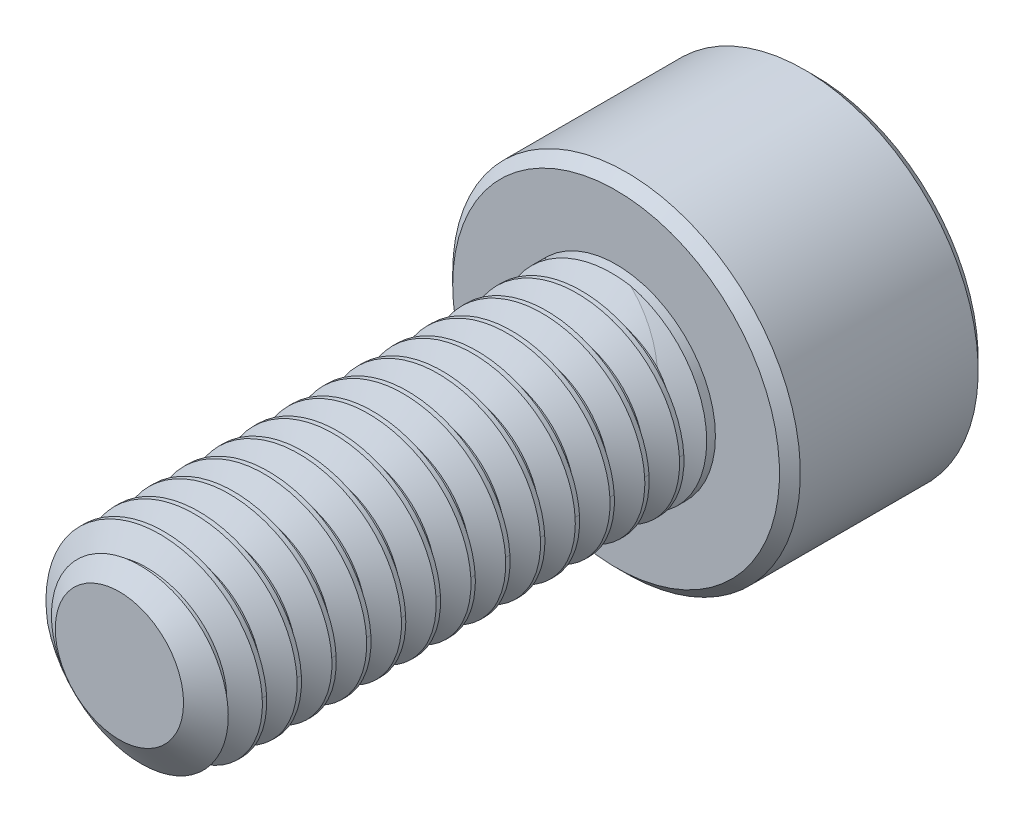
SolidWorks part; units mm, degrees
ref_plane "Front Plane" through (0, 0, 0) normal (0, 0, 1) x (1, 0, 0)
ref_plane "Top Plane" through (0, 0, 0) normal (0, 1, 0) x (1, 0, 0)
ref_plane "Right Plane" through (0, 0, 0) normal (1, 0, 0) x (0, 0, -1)
sketch "Sketch1" plane through (0, 0, 0) normal (0, 0, 1) x (1, 0, 0)
  circle A0 centre (0, 0) radius 2
  dimension "OD" = 4
extrude "Extrude1" add sketch "Sketch1" against normal blind 10
sketch "Sketch2" plane through (0, 0, 0) normal (0, 0, 1) x (1, 0, 0)
  circle A0 centre (0, 0) radius 2 construction
  circle A1 centre (0, 0) radius 2
curve "Helix/Spiral1" pitch 0.7 height 10.7 radius 2 centre (0, 0, 0) axis (0, 0, -1) start towards (0, 1, 0) parameters "pitch"=0.7
sketch "Sketch3" plane through (0, 0, 0) normal (1, 0, 0) x (0, 0, -1)
  line L0 (-0.6125, 2) -> (-0.35, 1.5453)
  line L1 (-0.35, 1.5453) -> (-0.2625, 1.5453)
  line L2 (-0.2625, 1.5453) -> (0, 2)
  line L3 (-0.6125, 2) -> (0, 2)
  line L4 (-0.3063, 2) -> (-0.3063, 1.5453) construction
  line L5 (-0.4813, 1.7727) -> (-0.1313, 1.7727) construction
  line L6 (0, 2) -> (0, -2) construction
  line L7 (0, -2) -> (10, -2) construction
  point P11 (3.15, -2)
  dimension "D1" = 0.0875
  dimension "D2" = 0.35
  dimension "D3" = 60
  dimension "D4" = 3.15
sweep "Cut-Sweep1" cut profiles "Sketch3" path "Helix/Spiral1" align with end faces yes
sketch "Sketch4" plane through (0, 0, 0) normal (1, 0, 0) x (0, 0, -1)
  line L0 (0.4962, 2) -> (0, 1.2913)
  line L1 (0, 1.2913) -> (0, 2)
  line L2 (0.4962, 2) -> (0, 2)
  line L3 (-0.6125, 2) -> (0, 2) construction
  line L4 (0, 0) -> (7.0209, 0) construction
  dimension "D1" = 55
  dimension "D2" = 0.254
revolve "Cut-Revolve1" cut sketch "Sketch4" angle 360 about L4
sketch "Sketch5" plane through (0, 0, 0) normal (1, 0, 0) x (0, 0, -1)
  line L0 (10, 0.3311) -> (10, 1.814) construction
  line L1 (10, 2) -> (0.1203, 2)
  line L2 (10, 2) -> (10, 0)
  line L3 (10, 0) -> (0.0001, 0)
  line L4 (0.0001, 1.6698) -> (0.0001, 0)
  line L5 (0.1203, 2) -> (0.0001, 1.6698)
  line L6 (0, 0) -> (9.9695, 0) construction
  point P3 (0.0001, 2)
  point P10 (0.0001, 2)
  dimension "D1" = 0.3302
  dimension "Thread min" = 0.0001
  dimension "D3" = 20
revolve "partially thread" [suppressed] add sketch "Sketch5" angle 360 about L6
sketch "Sketch6" plane through (0, 0, -10) normal (0, 0, -1) x (-1, 0, 0)
  circle A0 centre (0, 0) radius 3.5
  dimension "head dia" = 7
extrude "Extrude2" add sketch "Sketch6" along normal blind 4
sketch "Sketch7" plane through (0, 0, -14) normal (0, 0, -1) x (-1, 0, 0)
  line L1 (0, 1.7321) -> (-1.5, 0.866)
  line L2 (-1.5, 0.866) -> (-1.5, -0.866)
  line L3 (-1.5, -0.866) -> (0, -1.7321)
  line L4 (0, -1.7321) -> (1.5, -0.866)
  line L5 (1.5, -0.866) -> (1.5, 0.866)
  line L6 (1.5, 0.866) -> (0, 1.7321)
  circle A0 centre (0, 0) radius 1.5 construction
  dimension "hex dia" = 3
extrude "Cut-Extrude1" cut sketch "Sketch7" against normal blind 2.25
sketch "Sketch8" plane through (0, 0, -14) normal (0, 0, -1) x (-1, 0, 0)
  circle A0 centre (0, 0) radius 1.7321
extrude "Cut-Extrude2" cut sketch "Sketch8" against normal through all draft 45
chamfer "Chamfer1" distance 0.21 angle 45 2 edges at (-3.5, 0, -14) (-3.5, 0, -10)
sketch "Sketch9" plane through (0, 0, 0) normal (1, 0, 0) x (0, 0, -1)
  line L0 (0, 2) -> (0, -2) construction
  line L1 (3.85, 2) -> (3.85, -2) construction
  dimension "D1" = 3.85
sketch "Sketch10" plane through (0, 0, 0) normal (1, 0, 0) x (0, 0, -1)
  line L0 (10, 2) -> (10, 0)
  line L1 (10, 2) -> (9.825, 2)
  line L2 (9.825, 2) -> (8.9966, 0)
  line L3 (10, 0) -> (8.9966, 0)
  line L4 (10, 3.29) -> (10, -3.29) construction
  dimension "D1" = 22.5
  dimension "D2" = 0.175
revolve "Revolve1" add sketch "Sketch10" angle 360 about L3
equation "\"D3@Helix/Spiral1\" = \"screw length@Extrude1\"+\"pitch@Helix/Spiral1\""
equation "\"D1@Sketch3\" = \"pitch@Helix/Spiral1\"*.125"
equation "\"D2@Sketch3\" = \"pitch@Helix/Spiral1\"*.5"
equation "\"D1@Cut-Extrude1\" = \"hex dia@Sketch7\"*.75"
equation "\"D1@Chamfer1\" = \"head dia@Sketch6\"*.03"
equation "\"D1@Sketch9\" = \"pitch@Helix/Spiral1\"*5.5"
equation "\"D2@Sketch10\" = \"pitch@Helix/Spiral1\"*.25"
equation "\"D4@Sketch3\" = \"pitch@Helix/Spiral1\"*4.50"
